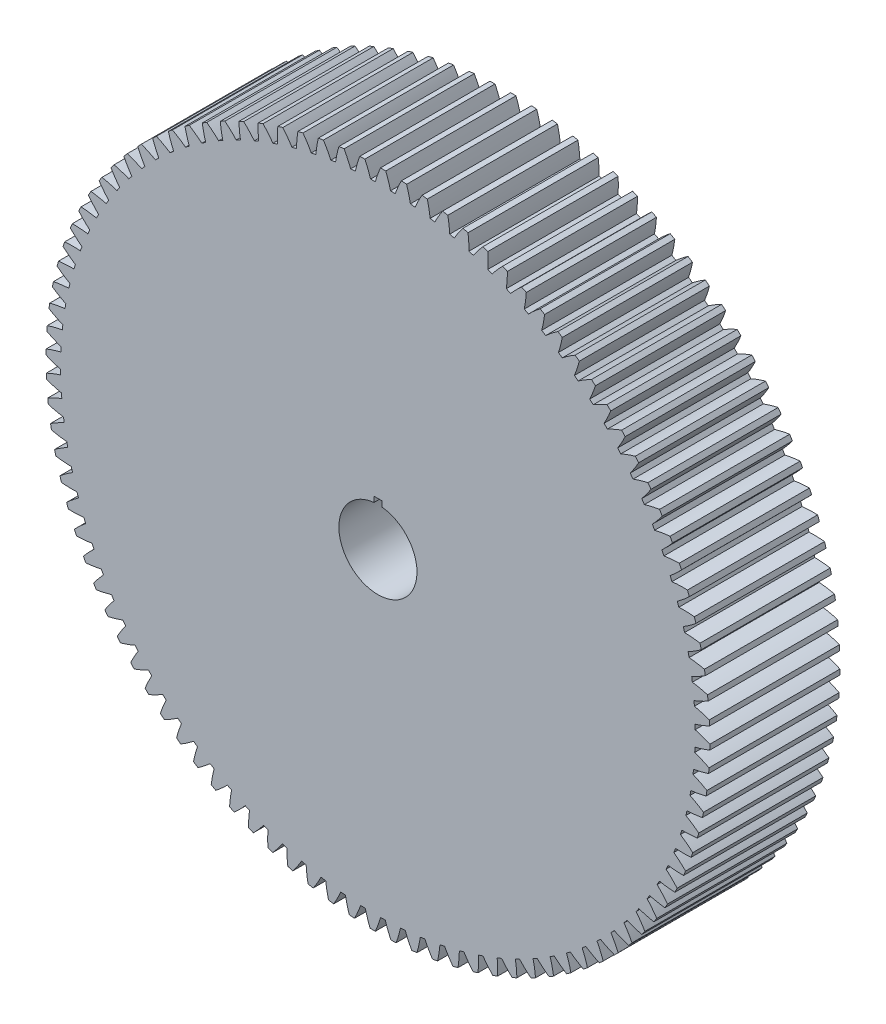
SolidWorks part; units mm, degrees
ref_plane "前视基准面" through (0, 0, 0) normal (0, 0, 1) x (1, 0, 0)
ref_plane "上视基准面" through (0, 0, 0) normal (0, 1, 0) x (1, 0, 0)
ref_plane "右视基准面" through (0, 0, 0) normal (1, 0, 0) x (0, 0, -1)
other "Configuration Table"
sketch "草图1" plane through (0, 0, 0) normal (0, 0, 1) x (1, 0, 0)
  circle A0 centre (0, 0) radius 121.875
  circle A1 centre (0, 0) radius 127.5
  circle A2 centre (0, 0) radius 125 construction
  dimension "D1" = 255
  dimension "D2" = 250
  dimension "D3" = 243.75
extrude "凸台-拉伸1" add sketch "草图1" along normal blind 50 contours A0 region at (0, 0, 0)
sketch "草图2" plane through (0, 0, 50) normal (0, 0, 1) x (1, 0, 0)
  line L0 (0, 0) -> (0, 157.6225) construction
  line L1 (0, 0) -> (57.1151, 156.9224) construction
  line L2 (0, 0) -> (2.6496, 168.6624) construction
  line L3 (0, 125) -> (40.1742, 110.3778) construction
  circle A0 centre (0, 0) radius 127.5 construction
  circle A1 centre (0, 0) radius 125 construction
  arc A2 (3.0068, 127.4645) -> (0.9985, 127.4961) centre (0, 0) ccw
  circle A3 centre (0, 0) radius 125 construction
  circle A4 centre (0, 0) radius 121.875 construction
  arc A5 (4.8321, 121.7792) -> (-1.0045, 121.8709) centre (0, 0) ccw
  arc A6 (0.9985, 127.4961) -> (-1.0045, 121.8709) centre (40.1742, 110.3778) ccw
  arc A7 (3.0068, 127.4645) -> (4.8321, 121.7792) centre (-36.6874, 111.5852) cw
  dimension "D1" = 20
  dimension "D2" = 0.9
extrude "凸台-拉伸2" add sketch "草图2" against normal blind 50
pattern_circular "阵列(圆周)1" count 100 over 360 about axis through (0, 0, 50) along (0, 0, 1) of "凸台-拉伸2"
sketch "草图3" plane through (0, 0, 0) normal (0, 0, 1) x (1, 0, 0)
  line L2 (-1.5, 14.9248) -> (-1.5, 17)
  line L3 (-1.5, 17) -> (1.5, 17)
  line L4 (1.5, 14.9248) -> (1.5, 17)
  arc A0 (-1.5, 14.9248) -> (1.5, 14.9248) centre (0, 0) ccw
  dimension "D1" = 30
  dimension "D2" = 17
  dimension "D3" = 3
  dimension "D4" = 1.5
extrude "切除-拉伸1" cut sketch "草图3" along normal through all
